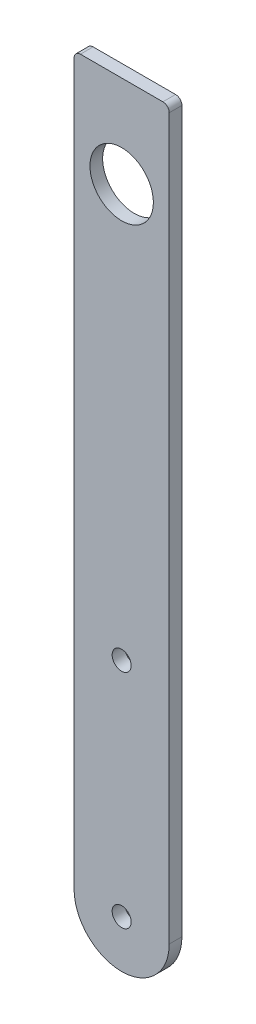
SolidWorks part; units mm, degrees
ref_plane "Front Plane" through (0, 0, 0) normal (0, 0, 1) x (1, 0, 0)
ref_plane "Top Plane" through (0, 0, 0) normal (0, 1, 0) x (1, 0, 0)
ref_plane "Right Plane" through (0, 0, 0) normal (1, 0, 0) x (0, 0, -1)
sketch "Sketch2" plane through (0, 0, 0) normal (0, 0, 1) x (1, 0, 0)
  line L0 (7.5, 6.5) -> (7.5, 106.5)
  line L2 (0, 6.5) -> (0, 100)
  line L4 (15, 6.5) -> (15, 100)
  line L8 (7.5, 121) -> (15, 121)
  line L9 (15, 121) -> (15, 100)
  line L10 (7.5, 121) -> (0, 121)
  line L11 (0, 121) -> (0, 100)
  arc A0 (0, 6.5) -> (15, 6.5) centre (7.5, 6.5) ccw
  circle A1 centre (7.5, 6.5) radius 1.5
  circle A2 centre (7.5, 106.5) radius 5
  dimension "D1" = 10
  dimension "D5" = 7.5
  dimension "D6" = 3
  dimension "D2" = 100
  dimension "D3" = 14.5
  dimension "D4" = 15
  dimension "D7" = 15
  dimension "D8" = 7.5
  dimension "D9" = 7.5
extrude "Boss-Extrude2" add sketch "Sketch2" along normal blind 2 contours L2 A0 L4 L9 L8 L10 L11 A2 A1 region at (1.2292, 53.25, 0)
sketch "Sketch3" plane through (0, 0, 2) normal (0, 0, 1) x (1, 0, 0)
  line L0 (7.5, 111.5) -> (7.5, 116.5)
  line L1 (7.5, 101.5) -> (7.5, 41.5)
  circle A0 centre (7.5, 106.5) radius 5 construction
  circle A2 centre (7.5, 41.5) radius 1.5
  dimension "D1" = 60
  dimension "D2" = 5
extrude "Cut-Extrude1" cut sketch "Sketch3" against normal blind 2 contours A2 region at (6.4693, 40.4693, 2)
fillet "Fillet1" radius 1 2 edges at (15, 121, 1) (0, 121, 1)
